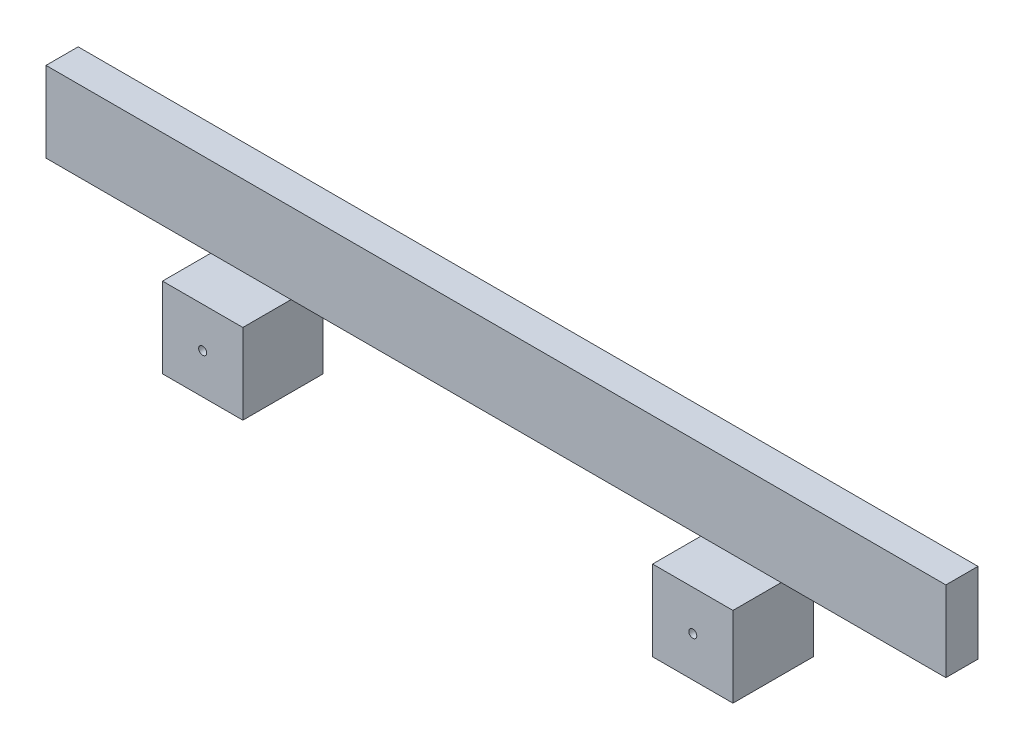
SolidWorks part; units mm, degrees
ref_plane "Plan de face" through (0, 0, 0) normal (0, 0, 1) x (1, 0, 0)
ref_plane "Plan de dessus" through (0, 0, 0) normal (0, 1, 0) x (1, 0, 0)
ref_plane "Plan de droite" through (0, 0, 0) normal (1, 0, 0) x (0, 0, -1)
sketch "Esquisse1" plane through (0, 0, 0) normal (0, 0, 1) x (1, 0, 0)
  line L1 (0, 0) -> (280, 0)
  line L2 (0, 0) -> (0, 25)
  line L3 (0, 25) -> (280, 25)
  line L4 (280, 0) -> (280, 25)
  line L5 (51.25, 0) -> (76.25, 0)
  line L6 (51.25, 0) -> (51.25, -25)
  line L7 (51.25, -25) -> (76.25, -25)
  line L8 (76.25, 0) -> (76.25, -25)
  line L9 (203.75, 0) -> (228.75, 0)
  line L10 (203.75, 0) -> (203.75, -25)
  line L11 (203.75, -25) -> (228.75, -25)
  line L12 (228.75, 0) -> (228.75, -25)
  circle A0 centre (63.75, -12.5) radius 1.25
  circle A1 centre (216.25, -12.5) radius 1.25
  dimension "D9" = 2.5
  dimension "D10" = 2.5
  dimension "D1" = 280
  dimension "D2" = 25
  dimension "D3" = 25
  dimension "D4" = 25
  dimension "D5" = 25
  dimension "D6" = 25
  dimension "D7" = 51.25
  dimension "D8" = 51.25
  dimension "D11" = 12.5
  dimension "D12" = 12.5
  dimension "D13" = 63.75
  dimension "D14" = 12.5
extrude "Boss.-Extru.2" add sketch "Esquisse1" along normal blind 25 contours L8 L1 L6 L7 region at (63.75, -0.3536, 0)
extrude "Boss.-Extru.3" add sketch "Esquisse1<5>" along normal blind 25 separate body contours L12 L1 L10 L11 region at (216.25, -0.3536, 0)
sketch "Esquisse1<5>" plane through (0, 0, 0) normal (0, 0, 1) x (1, 0, 0) same geometry as "Esquisse1"
extrude "Boss.-Extru.4" add sketch "Esquisse1<7>" along normal blind 10 contours L1 L4 L3 L2 region at (140, 12.5, 0)
sketch "Esquisse1<7>" plane through (0, 0, 0) normal (0, 0, 1) x (1, 0, 0) same geometry as "Esquisse1"
